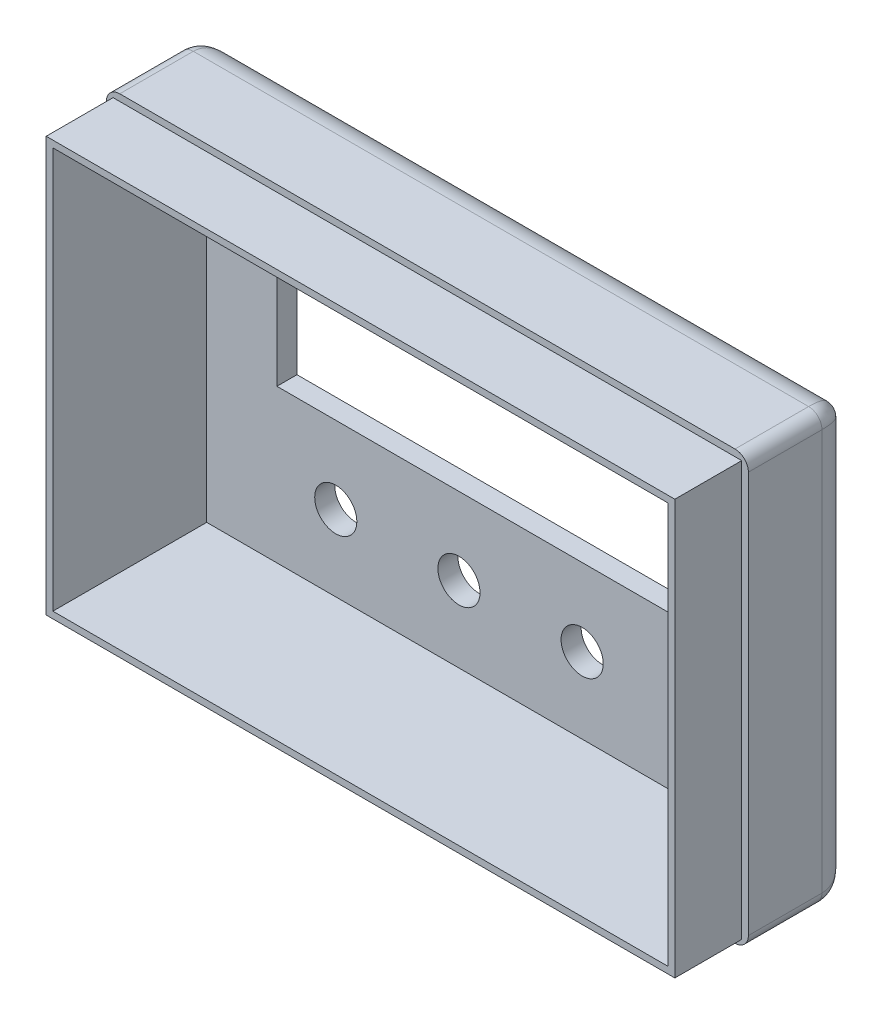
SolidWorks part; units mm, degrees
ref_plane "Front Plane" through (0, 0, 0) normal (0, 0, 1) x (1, 0, 0)
ref_plane "Top Plane" through (0, 0, 0) normal (0, 1, 0) x (1, 0, 0)
ref_plane "Right Plane" through (0, 0, 0) normal (1, 0, 0) x (0, 0, -1)
sketch "Sketch1" plane through (0, 0, 0) normal (0, 0, 1) x (1, 0, 0)
  line L1 (-46, 30) -> (46, 30)
  line L2 (-46, 30) -> (-46, -30)
  line L3 (-46, -30) -> (46, -30)
  line L4 (46, 30) -> (46, -30)
  line L5 (-46, 30) -> (46, -30) construction
  line L6 (-46, -30) -> (46, 30) construction
  point P0 (0, 0)
  dimension "D1" = 92
  dimension "D2" = 60
extrude "Boss-Extrude1" add sketch "Sketch1" along normal blind 3
sketch "Sketch2" plane through (0, 0, 3) normal (0, 0, 1) x (1, 0, 0)
  line L0 (-46, 32) -> (46, 32)
  line L1 (-46, 30) -> (46, 30)
  line L2 (-46, 30) -> (-46, -30)
  line L3 (-46, -30) -> (46, -30)
  line L4 (46, 30) -> (46, -30)
  line L5 (48, 30) -> (48, -30)
  line L6 (-46, -32) -> (46, -32)
  line L7 (-48, 30) -> (-48, -30)
  line L16 (-48, 32) -> (48, 32) construction
  line L17 (48, 32) -> (48, -32) construction
  line L18 (-48, 32) -> (-48, -32) construction
  line L19 (-48, -32) -> (48, -32) construction
  arc A0 (46, -32) -> (48, -30) centre (46, -30) ccw
  arc A1 (46, 32) -> (48, 30) centre (46, 30) cw
  arc A2 (-46, 32) -> (-48, 30) centre (-46, 30) ccw
  arc A3 (-48, -30) -> (-46, -32) centre (-46, -30) ccw
  dimension "D1" = 2
extrude "Boss-Extrude2" add sketch "Sketch2" along normal blind 23 and the other way blind 3
sketch "Sketch4" plane through (0, 0, 26) normal (0, 0, 1) x (1, 0, 0)
  line L7 (-47, 31) -> (47, 31)
  line L8 (-47, 31) -> (-47, -31)
  line L9 (-47, -31) -> (47, -31)
  line L10 (47, 31) -> (47, -31)
  line L11 (-52.2415, 35.2749) -> (56.6159, 35.2749)
  line L12 (-52.2415, 35.2749) -> (-52.2415, -38.0756)
  line L13 (-52.2415, -38.0756) -> (56.6159, -38.0756)
  line L14 (56.6159, 35.2749) -> (56.6159, -38.0756)
extrude "Cut-Extrude1" cut sketch "Sketch4" against normal blind 10
sketch "Sketch10" plane through (0, 0, 0) normal (0, 0, -1) x (-1, 0, 0)
  line L0 (-34.2658, -18.6771) -> (50.6815, -18.6771) construction
  line L1 (-35.5, 16.8729) -> (35.5, 16.8729)
  line L2 (-35.5, 16.8729) -> (-35.5, -7.1271)
  line L3 (-35.5, -7.1271) -> (35.5, -7.1271)
  line L4 (35.5, 16.8729) -> (35.5, -7.1271)
  line L7 (0, 32) -> (0, -45.7931) construction
  line L8 (-46, 32) -> (46, 32) construction
  line L10 (48, 0) -> (-80.467, -1.1886) construction
  line L11 (48, 30) -> (48, -30) construction
  circle A0 centre (-28.56, -18.6771) radius 3.15
  circle A1 centre (-10.14, -18.6771) radius 3.15
  circle A2 centre (8.28, -18.6771) radius 3.15
  circle A3 centre (26.7, -18.6771) radius 3.15
  point P14 (0, 16.8729)
  dimension "D3" = 6.3
  dimension "D4" = 6.3
  dimension "D5" = 6.3
  dimension "D6" = 6.3
  dimension "D8" = 18.42
  dimension "D9" = 18.42
  dimension "D1" = 71
  dimension "D2" = 24
  dimension "D7" = 18.42
  dimension "D10" = 11.55
  dimension "D11" = 6.94
extrude "Cut-Extrude3" cut sketch "Sketch10" against normal blind 10
fillet "Fillet1" radius 5 8 edges at (-47.4142, -31.4142, 0) (47.4142, 31.4142, 0) (47.4142, -31.4142, 0) (48, 0, 0) (0, -32, 0) (-48, 0, 0) (-47.4142, 31.4142, 0) (0, 32, 0)
